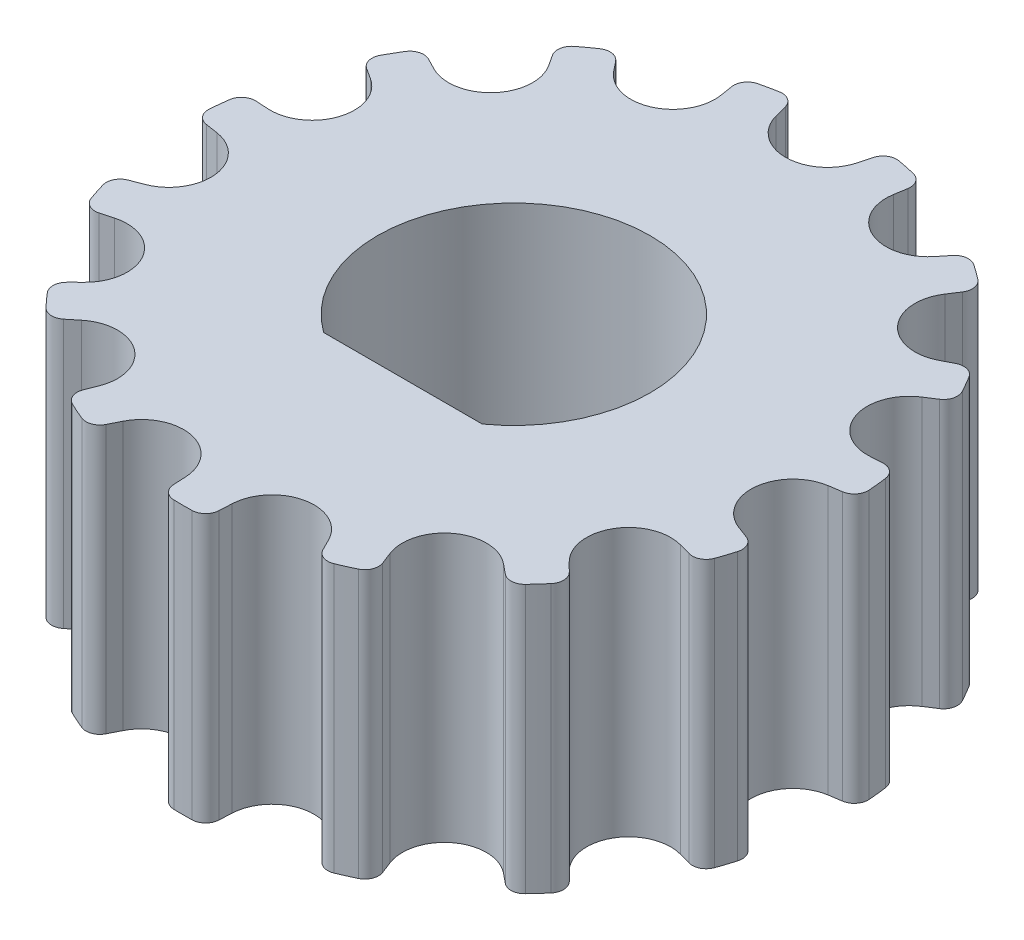
SolidWorks part; units mm, degrees
material "Acrylic (Medium-high impact)"
ref_plane "Front Plane" through (0, 0, 0) normal (0, 0, 1) x (1, 0, 0)
ref_plane "Top Plane" through (0, 0, 0) normal (0, 1, 0) x (1, 0, 0)
ref_plane "Right Plane" through (0, 0, 0) normal (1, 0, 0) x (0, 0, -1)
sketch "Sketch1" plane through (0, 0, 0) normal (0, 1, 0) x (1, 0, 0)
  circle A0 centre (0, 0) radius 7.162
  dimension "D1" = 14.3239
extrude "Boss-Extrude1" add sketch "Sketch1" along normal blind 5.8
sketch "Sketch2" plane through (0, 5.8, 0) normal (0, 1, 0) x (1, 0, 0)
  line L0 (0, 0) -> (0, 7.162) construction
  line L1 (-0.8799, 6.5598) -> (-0.95, 6.8255)
  line L2 (-2.913, 6.5428) -> (-2.913, 7.162)
  line L3 (-2.913, 7.162) -> (2.913, 7.162)
  line L4 (0.8799, 6.5598) -> (0.95, 6.8255)
  line L5 (2.913, 6.5428) -> (2.913, 7.162)
  circle A0 centre (0, 0) radius 7.162 construction
  arc A1 (0.8799, 6.5598) -> (-0.8799, 6.5598) centre (0, 6.792) cw
  arc A2 (-0.95, 6.8255) -> (-1.2943, 7.0441) centre (-1.2401, 6.749) ccw
  arc A4 (0.95, 6.8255) -> (1.2943, 7.0441) centre (1.2401, 6.749) cw
  arc A5 (-1.2943, 7.0441) -> (-2.913, 6.5428) centre (0, 0) ccw
  arc A6 (1.2943, 7.0441) -> (2.913, 6.5428) centre (0, 0) cw
  point P11 (0, 7.162)
  point P19 (0, 5.882)
  dimension "D3" = 0.3
  dimension "D5" = 0.91
  dimension "D2" = 0.95
  dimension "D4" = 1.28
  dimension "D6" = 24
extrude "Cut-Extrude1" cut sketch "Sketch2" against normal through all
pattern_circular "CirPattern1" count 15 over 360 about axis through (0, 5.8, 0) along (0, -1, 0) of "Cut-Extrude1"
sketch "Sketch3" plane through (0, 0, 0) normal (0, -1, 0) x (1, 0, 0)
  line L0 (1.7154, 2.4) -> (-1.7154, 2.4)
  arc A0 (-1.7154, 2.4) -> (1.7154, 2.4) centre (0, 0) ccw
  dimension "D1" = 5.9
  dimension "D2" = 2.4
extrude "Cut-Extrude2" cut sketch "Sketch3" against normal through all
sketch "Sketch5" plane through (0, 0, 0) normal (0, -1, 0) x (1, 0, 0)
  line L60 (5.4179, -3.8244) -> (5.6623, -3.9501)
  line L61 (6.252, -2.9286) -> (6.021, -2.7798)
  line L62 (6.505, -1.2901) -> (6.7794, -1.3055)
  line L63 (6.9027, -0.1325) -> (6.6311, -0.0906)
  line L64 (6.4674, 1.4673) -> (6.7243, 1.5648)
  line L65 (6.3598, 2.6865) -> (6.0946, 2.6144)
  line L66 (5.3115, 3.9709) -> (5.5065, 4.1645)
  line L67 (4.7173, 5.041) -> (4.5044, 4.8673)
  line L68 (3.2371, 5.788) -> (3.3366, 6.0442)
  line L69 (2.2591, 6.5239) -> (2.1352, 6.2786)
  line L70 (0.6031, 6.6042) -> (0.5897, 6.8787)
  line L71 (-0.5897, 6.8787) -> (-0.6031, 6.6042)
  line L72 (-2.1352, 6.2786) -> (-2.2591, 6.5239)
  line L73 (-3.3366, 6.0442) -> (-3.2371, 5.788)
  line L74 (-4.5044, 4.8673) -> (-4.7173, 5.041)
  line L75 (-5.5065, 4.1645) -> (-5.3115, 3.9709)
  line L76 (-6.0946, 2.6144) -> (-6.3598, 2.6865)
  line L77 (-6.7243, 1.5648) -> (-6.4674, 1.4673)
  line L78 (-6.6311, -0.0906) -> (-6.9027, -0.1325)
  line L79 (-6.7794, -1.3055) -> (-6.505, -1.2901)
  line L80 (-6.021, -2.7798) -> (-6.252, -2.9286)
  line L81 (-5.6623, -3.9501) -> (-5.4179, -3.8244)
  line L82 (-4.3698, -4.9885) -> (-4.5203, -5.2184)
  line L83 (-3.5661, -5.9117) -> (-3.394, -5.6974)
  line L84 (-1.963, -6.3345) -> (-2.007, -6.6058)
  line L85 (-0.8533, -6.851) -> (-0.7832, -6.5853)
  line L86 (0.7832, -6.5853) -> (0.8533, -6.851)
  line L87 (2.007, -6.6058) -> (1.963, -6.3345)
  line L88 (3.394, -5.6974) -> (3.5661, -5.9117)
  line L89 (4.5203, -5.2184) -> (4.3698, -4.9885)
  line L90 (5.4179, -3.8244) -> (5.6623, -3.9501)
  line L91 (6.252, -2.9286) -> (6.021, -2.7798)
  line L92 (6.505, -1.2901) -> (6.7794, -1.3055)
  line L93 (6.9027, -0.1325) -> (6.6311, -0.0906)
  line L94 (6.4674, 1.4673) -> (6.7243, 1.5648)
  line L95 (6.3598, 2.6865) -> (6.0946, 2.6144)
  line L96 (5.3115, 3.9709) -> (5.5065, 4.1645)
  line L97 (4.7173, 5.041) -> (4.5044, 4.8673)
  line L98 (3.2371, 5.788) -> (3.3366, 6.0442)
  line L99 (2.2591, 6.5239) -> (2.1352, 6.2786)
  line L100 (0.6031, 6.6042) -> (0.5897, 6.8787)
  line L101 (-0.5897, 6.8787) -> (-0.6031, 6.6042)
  line L102 (-2.1352, 6.2786) -> (-2.2591, 6.5239)
  line L103 (-3.3366, 6.0442) -> (-3.2371, 5.788)
  line L104 (-4.5044, 4.8673) -> (-4.7173, 5.041)
  line L105 (-5.5065, 4.1645) -> (-5.3115, 3.9709)
  line L106 (-6.0946, 2.6144) -> (-6.3598, 2.6865)
  line L107 (-6.7243, 1.5648) -> (-6.4674, 1.4673)
  line L108 (-6.6311, -0.0906) -> (-6.9027, -0.1325)
  line L109 (-6.7794, -1.3055) -> (-6.505, -1.2901)
  line L110 (-6.021, -2.7798) -> (-6.252, -2.9286)
  line L111 (-5.6623, -3.9501) -> (-5.4179, -3.8244)
  line L112 (-4.3698, -4.9885) -> (-4.5203, -5.2184)
  line L113 (-3.5661, -5.9117) -> (-3.394, -5.6974)
  line L114 (-1.963, -6.3345) -> (-2.007, -6.6058)
  line L115 (-0.8533, -6.851) -> (-0.7832, -6.5853)
  line L116 (0.7832, -6.5853) -> (0.8533, -6.851)
  line L117 (2.007, -6.6058) -> (1.963, -6.3345)
  line L118 (3.394, -5.6974) -> (3.5661, -5.9117)
  line L119 (4.5203, -5.2184) -> (4.3698, -4.9885)
  circle A60 centre (0, 0) radius 3.9038
  arc A120 (5.6623, -3.9501) -> (6.186, -3.8039) centre (5.8452, -3.5944) ccw
  arc A121 (6.186, -3.8039) -> (6.3873, -3.4553) centre (0, 0) ccw
  arc A122 (6.3873, -3.4553) -> (6.252, -2.9286) centre (6.0355, -3.2649) ccw
  arc A123 (6.505, -1.2901) -> (6.021, -2.7798) centre (6.4595, -2.0988) ccw
  arc A124 (6.7794, -1.3055) -> (7.1984, -0.959) centre (6.8019, -0.9062) ccw
  arc A125 (7.1984, -0.959) -> (7.2405, -0.5586) centre (0, 0) ccw
  arc A126 (7.2405, -0.5586) -> (6.9027, -0.1325) centre (6.8416, -0.5278) ccw
  arc A127 (6.4674, 1.4673) -> (6.6311, -0.0906) centre (6.7548, 0.71) ccw
  arc A128 (6.7243, 1.5648) -> (6.9661, 2.0518) centre (6.5824, 1.9387) ccw
  arc A129 (6.9661, 2.0518) -> (6.8417, 2.4347) centre (0, 0) ccw
  arc A130 (6.8417, 2.4347) -> (6.3598, 2.6865) centre (6.4648, 2.3006) ccw
  arc A131 (5.3115, 3.9709) -> (6.0946, 2.6144) centre (5.882, 3.396) ccw
  arc A132 (5.5065, 4.1645) -> (5.5293, 4.7077) centre (5.2248, 4.4484) ccw
  arc A133 (5.5293, 4.7077) -> (5.2599, 5.0069) centre (0, 0) ccw
  arc A134 (5.2599, 5.0069) -> (4.7173, 5.041) centre (4.9702, 4.7312) ccw
  arc A135 (3.2371, 5.788) -> (4.5044, 4.8673) centre (3.9922, 5.4948) ccw
  arc A136 (3.3366, 6.0442) -> (3.1365, 6.5497) centre (2.9637, 6.1889) ccw
  arc A137 (3.1365, 6.5497) -> (2.7687, 6.7135) centre (0, 0) ccw
  arc A138 (2.7687, 6.7135) -> (2.2591, 6.5239) centre (2.6162, 6.3437) ccw
  arc A139 (0.6031, 6.6042) -> (2.1352, 6.2786) centre (1.4121, 6.6436) ccw
  arc A140 (0.5897, 6.8787) -> (0.2013, 7.2592) centre (0.1902, 6.8593) ccw
  arc A141 (0.2013, 7.2592) -> (-0.2013, 7.2592) centre (0, 0) ccw
  arc A142 (-0.2013, 7.2592) -> (-0.5897, 6.8787) centre (-0.1902, 6.8593) ccw
  arc A143 (-2.1352, 6.2786) -> (-0.6031, 6.6042) centre (-1.4121, 6.6436) ccw
  arc A144 (-2.2591, 6.5239) -> (-2.7687, 6.7135) centre (-2.6162, 6.3437) ccw
  arc A145 (-2.7687, 6.7135) -> (-3.1365, 6.5497) centre (0, 0) ccw
  arc A146 (-3.1365, 6.5497) -> (-3.3366, 6.0442) centre (-2.9637, 6.1889) ccw
  arc A147 (-4.5044, 4.8673) -> (-3.2371, 5.788) centre (-3.9922, 5.4948) ccw
  arc A148 (-4.7173, 5.041) -> (-5.2599, 5.0069) centre (-4.9702, 4.7312) ccw
  arc A149 (-5.2599, 5.0069) -> (-5.5293, 4.7077) centre (0, 0) ccw
  arc A150 (-5.5293, 4.7077) -> (-5.5065, 4.1645) centre (-5.2248, 4.4484) ccw
  arc A151 (-6.0946, 2.6144) -> (-5.3115, 3.9709) centre (-5.882, 3.396) ccw
  arc A152 (-6.3598, 2.6865) -> (-6.8417, 2.4347) centre (-6.4648, 2.3006) ccw
  arc A153 (-6.8417, 2.4347) -> (-6.9661, 2.0518) centre (0, 0) ccw
  arc A154 (-6.9661, 2.0518) -> (-6.7243, 1.5648) centre (-6.5824, 1.9387) ccw
  arc A155 (-6.6311, -0.0906) -> (-6.4674, 1.4673) centre (-6.7548, 0.71) ccw
  arc A156 (-6.9027, -0.1325) -> (-7.2405, -0.5586) centre (-6.8416, -0.5278) ccw
  arc A157 (-7.2405, -0.5586) -> (-7.1984, -0.959) centre (0, 0) ccw
  arc A158 (-7.1984, -0.959) -> (-6.7794, -1.3055) centre (-6.8019, -0.9062) ccw
  arc A159 (-6.021, -2.7798) -> (-6.505, -1.2901) centre (-6.4595, -2.0988) ccw
  arc A160 (-6.252, -2.9286) -> (-6.3873, -3.4553) centre (-6.0355, -3.2649) ccw
  arc A161 (-6.3873, -3.4553) -> (-6.186, -3.8039) centre (0, 0) ccw
  arc A162 (-6.186, -3.8039) -> (-5.6623, -3.9501) centre (-5.8452, -3.5944) ccw
  arc A163 (-4.3698, -4.9885) -> (-5.4179, -3.8244) centre (-5.0474, -4.5447) ccw
  arc A164 (-4.5203, -5.2184) -> (-4.4297, -5.7545) centre (-4.1857, -5.4375) ccw
  arc A165 (-4.4297, -5.7545) -> (-4.104, -5.9911) centre (0, 0) ccw
  arc A166 (-4.104, -5.9911) -> (-3.5661, -5.9117) centre (-3.8779, -5.6611) ccw
  arc A167 (-1.963, -6.3345) -> (-3.394, -5.6974) centre (-2.7625, -6.2048) ccw
  arc A168 (-2.007, -6.6058) -> (-1.7062, -7.0587) centre (-1.6122, -6.6699) ccw
  arc A169 (-1.7062, -7.0587) -> (-1.3124, -7.1424) centre (0, 0) ccw
  arc A170 (-1.3124, -7.1424) -> (-0.8533, -6.851) centre (-1.2401, -6.749) ccw
  arc A171 (0.7832, -6.5853) -> (-0.7832, -6.5853) centre (0, -6.792) ccw
  arc A172 (0.8533, -6.851) -> (1.3124, -7.1424) centre (1.2401, -6.749) ccw
  arc A173 (1.3124, -7.1424) -> (1.7062, -7.0587) centre (0, 0) ccw
  arc A174 (1.7062, -7.0587) -> (2.007, -6.6058) centre (1.6122, -6.6699) ccw
  arc A175 (3.394, -5.6974) -> (1.963, -6.3345) centre (2.7625, -6.2048) ccw
  arc A176 (3.5661, -5.9117) -> (4.104, -5.9911) centre (3.8779, -5.6611) ccw
  arc A177 (4.104, -5.9911) -> (4.4297, -5.7545) centre (0, 0) ccw
  arc A178 (4.4297, -5.7545) -> (4.5203, -5.2184) centre (4.1857, -5.4375) ccw
  arc A179 (5.4179, -3.8244) -> (4.3698, -4.9885) centre (5.0474, -4.5447) ccw
  arc A180 (5.6623, -3.9501) -> (6.186, -3.8039) centre (5.8452, -3.5944) ccw
  arc A181 (6.186, -3.8039) -> (6.3873, -3.4553) centre (0, 0) ccw
  arc A182 (6.3873, -3.4553) -> (6.252, -2.9286) centre (6.0355, -3.2649) ccw
  arc A183 (6.505, -1.2901) -> (6.021, -2.7798) centre (6.4595, -2.0988) ccw
  arc A184 (6.7794, -1.3055) -> (7.1984, -0.959) centre (6.8019, -0.9062) ccw
  arc A185 (7.1984, -0.959) -> (7.2405, -0.5586) centre (0, 0) ccw
  arc A186 (7.2405, -0.5586) -> (6.9027, -0.1325) centre (6.8416, -0.5278) ccw
  arc A187 (6.4674, 1.4673) -> (6.6311, -0.0906) centre (6.7548, 0.71) ccw
  arc A188 (6.7243, 1.5648) -> (6.9661, 2.0518) centre (6.5824, 1.9387) ccw
  arc A189 (6.9661, 2.0518) -> (6.8417, 2.4347) centre (0, 0) ccw
  arc A190 (6.8417, 2.4347) -> (6.3598, 2.6865) centre (6.4648, 2.3006) ccw
  arc A191 (5.3115, 3.9709) -> (6.0946, 2.6144) centre (5.882, 3.396) ccw
  arc A192 (5.5065, 4.1645) -> (5.5293, 4.7077) centre (5.2248, 4.4484) ccw
  arc A193 (5.5293, 4.7077) -> (5.2599, 5.0069) centre (0, 0) ccw
  arc A194 (5.2599, 5.0069) -> (4.7173, 5.041) centre (4.9702, 4.7312) ccw
  arc A195 (3.2371, 5.788) -> (4.5044, 4.8673) centre (3.9922, 5.4948) ccw
  arc A196 (3.3366, 6.0442) -> (3.1365, 6.5497) centre (2.9637, 6.1889) ccw
  arc A197 (3.1365, 6.5497) -> (2.7687, 6.7135) centre (0, 0) ccw
  arc A198 (2.7687, 6.7135) -> (2.2591, 6.5239) centre (2.6162, 6.3437) ccw
  arc A199 (0.6031, 6.6042) -> (2.1352, 6.2786) centre (1.4121, 6.6436) ccw
  arc A200 (0.5897, 6.8787) -> (0.2013, 7.2592) centre (0.1902, 6.8593) ccw
  arc A201 (0.2013, 7.2592) -> (-0.2013, 7.2592) centre (0, 0) ccw
  arc A202 (-0.2013, 7.2592) -> (-0.5897, 6.8787) centre (-0.1902, 6.8593) ccw
  arc A203 (-2.1352, 6.2786) -> (-0.6031, 6.6042) centre (-1.4121, 6.6436) ccw
  arc A204 (-2.2591, 6.5239) -> (-2.7687, 6.7135) centre (-2.6162, 6.3437) ccw
  arc A205 (-2.7687, 6.7135) -> (-3.1365, 6.5497) centre (0, 0) ccw
  arc A206 (-3.1365, 6.5497) -> (-3.3366, 6.0442) centre (-2.9637, 6.1889) ccw
  arc A207 (-4.5044, 4.8673) -> (-3.2371, 5.788) centre (-3.9922, 5.4948) ccw
  arc A208 (-4.7173, 5.041) -> (-5.2599, 5.0069) centre (-4.9702, 4.7312) ccw
  arc A209 (-5.2599, 5.0069) -> (-5.5293, 4.7077) centre (0, 0) ccw
  arc A210 (-5.5293, 4.7077) -> (-5.5065, 4.1645) centre (-5.2248, 4.4484) ccw
  arc A211 (-6.0946, 2.6144) -> (-5.3115, 3.9709) centre (-5.882, 3.396) ccw
  arc A212 (-6.3598, 2.6865) -> (-6.8417, 2.4347) centre (-6.4648, 2.3006) ccw
  arc A213 (-6.8417, 2.4347) -> (-6.9661, 2.0518) centre (0, 0) ccw
  arc A214 (-6.9661, 2.0518) -> (-6.7243, 1.5648) centre (-6.5824, 1.9387) ccw
  arc A215 (-6.6311, -0.0906) -> (-6.4674, 1.4673) centre (-6.7548, 0.71) ccw
  arc A216 (-6.9027, -0.1325) -> (-7.2405, -0.5586) centre (-6.8416, -0.5278) ccw
  arc A217 (-7.2405, -0.5586) -> (-7.1984, -0.959) centre (0, 0) ccw
  arc A218 (-7.1984, -0.959) -> (-6.7794, -1.3055) centre (-6.8019, -0.9062) ccw
  arc A219 (-6.021, -2.7798) -> (-6.505, -1.2901) centre (-6.4595, -2.0988) ccw
  arc A220 (-6.252, -2.9286) -> (-6.3873, -3.4553) centre (-6.0355, -3.2649) ccw
  arc A221 (-6.3873, -3.4553) -> (-6.186, -3.8039) centre (0, 0) ccw
  arc A222 (-6.186, -3.8039) -> (-5.6623, -3.9501) centre (-5.8452, -3.5944) ccw
  arc A223 (-4.3698, -4.9885) -> (-5.4179, -3.8244) centre (-5.0474, -4.5447) ccw
  arc A224 (-4.5203, -5.2184) -> (-4.4297, -5.7545) centre (-4.1857, -5.4375) ccw
  arc A225 (-4.4297, -5.7545) -> (-4.104, -5.9911) centre (0, 0) ccw
  arc A226 (-4.104, -5.9911) -> (-3.5661, -5.9117) centre (-3.8779, -5.6611) ccw
  arc A227 (-1.963, -6.3345) -> (-3.394, -5.6974) centre (-2.7625, -6.2048) ccw
  arc A228 (-2.007, -6.6058) -> (-1.7062, -7.0587) centre (-1.6122, -6.6699) ccw
  arc A229 (-1.7062, -7.0587) -> (-1.3124, -7.1424) centre (0, 0) ccw
  arc A230 (-1.3124, -7.1424) -> (-0.8533, -6.851) centre (-1.2401, -6.749) ccw
  arc A231 (0.7832, -6.5853) -> (-0.7832, -6.5853) centre (0, -6.792) ccw
  arc A232 (0.8533, -6.851) -> (1.3124, -7.1424) centre (1.2401, -6.749) ccw
  arc A233 (1.3124, -7.1424) -> (1.7062, -7.0587) centre (0, 0) ccw
  arc A234 (1.7062, -7.0587) -> (2.007, -6.6058) centre (1.6122, -6.6699) ccw
  arc A235 (3.394, -5.6974) -> (1.963, -6.3345) centre (2.7625, -6.2048) ccw
  arc A236 (3.5661, -5.9117) -> (4.104, -5.9911) centre (3.8779, -5.6611) ccw
  arc A237 (4.104, -5.9911) -> (4.4297, -5.7545) centre (0, 0) ccw
  arc A238 (4.4297, -5.7545) -> (4.5203, -5.2184) centre (4.1857, -5.4375) ccw
  arc A239 (5.4179, -3.8244) -> (4.3698, -4.9885) centre (5.0474, -4.5447) ccw
  dimension "D1" = 0.1
extrude "Boss-Extrude2" [suppressed] add sketch "Sketch5" against normal up to surface (5.8 mm away) up to face at (0, 5.8, -0.275)
sketch "Sketch6" plane through (0, 5.8, 0) normal (0, 1, 0) x (1, 0, 0)
  circle A0 centre (0, -10) radius 2.5
  dimension "D1" = 5
  dimension "D2" = 10
extrude "Cut-Extrude3" [suppressed] cut sketch "Sketch6" against normal through all
equation "\"smallPulleyTeeth\"= 15"
equation "\"largePulleyTeeth\"= 30"
equation "\"eighthThick\"= 2.9mm"
equation "\"D1@Sketch1\"=3*\"smallPulleyTeeth\"/pi"
equation "\"D1@Boss-Extrude1\" = \"eighthThick\" * 2"
equation "\"D6@Sketch2\"=360/\"smallPulleyTeeth\""
equation "\"quarterThick\"=6.0mm"
equation "\"D1@CirPattern1\"=\"smallPulleyTeeth\""
equation "\"sixteenthThick\" = 1.7mm"
equation "\"OD\" = 146mm"
equation "\"puckAngle\" = 60.5deg"
equation "\"puckDiam\" = 76.5mm"
equation "\"axlePress\" = 5.9mm"
equation "\"press\" = 0.2mm"
equation "\"wheelClear\" = 0.3mm"
equation "\"10-32clear\" = 4.8mm"
equation "\"6-32clear\" = 3.3mm"
equation "\"8-32clear\" = 4.0mm"
equation "\"wheelHeight\" = 22mm"
equation "\"D1@Sketch3\"=\"axlePress\""
